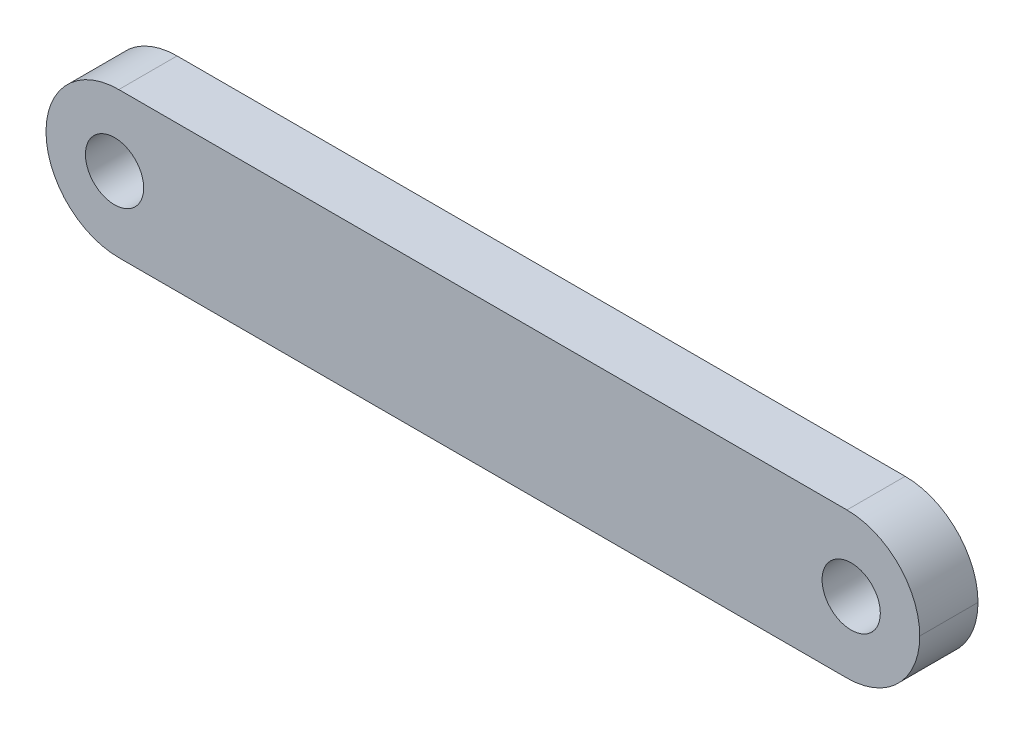
SolidWorks part; units mm, degrees
ref_plane "Front Plane" through (0, 0, 0) normal (0, 0, 1) x (1, 0, 0)
ref_plane "Top Plane" through (0, 0, 0) normal (0, 1, 0) x (1, 0, 0)
ref_plane "Right Plane" through (0, 0, 0) normal (1, 0, 0) x (0, 0, -1)
sketch "Sketch1" plane through (0, 0, 0) normal (0, 0, 1) x (1, 0, 0)
  line L0 (0, 7.3211) -> (0, -7.6539) construction
  line L1 (-15, 2.5) -> (15, 2.5)
  line L2 (-15, 2.5) -> (-15, -2.5)
  line L3 (-15, -2.5) -> (15, -2.5)
  line L4 (15, 2.5) -> (15, -2.5)
  line L5 (-15, 2.5) -> (15, -2.5) construction
  line L6 (-15, -2.5) -> (15, 2.5) construction
  circle A0 centre (12.6461, 0) radius 1
  circle A1 centre (-12.6461, 0) radius 1
  point P0 (0, 0)
  point P12 (0, 0)
  point P13 (12.6461, 0)
  dimension "D1" = 30
  dimension "D2" = 5
extrude "Boss-Extrude1" add sketch "Sketch1" along normal blind 2
fillet "Fillet1" radius 2.5 4 edges at (-15, -2.5, 1) (-15, 2.5, 1) (15, -2.5, 1) (15, 2.5, 1)
sketch "Sketch2" plane through (0, 0, 0) normal (0, 0, 1) x (1, 0, 0)
  circle A0 centre (0, 0) radius 1
